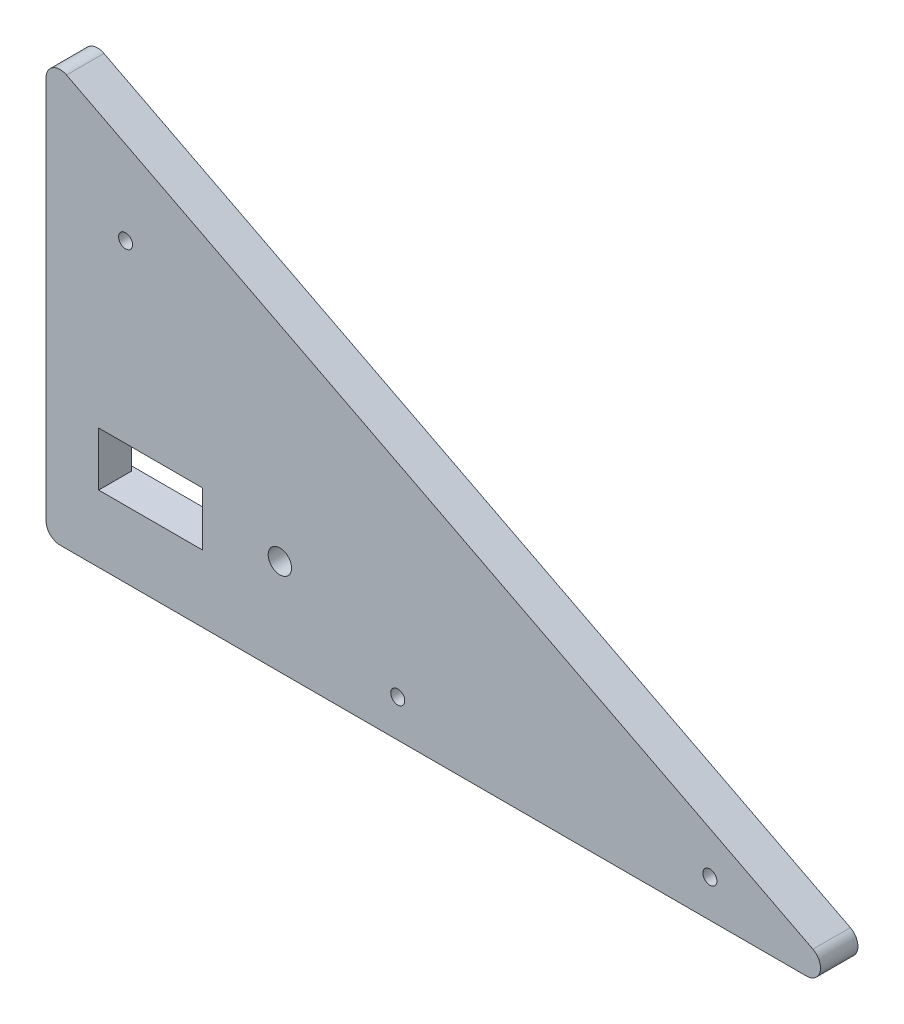
SolidWorks part; units mm, degrees
ref_plane "Front Plane" through (0, 0, 0) normal (0, 0, 1) x (1, 0, 0)
ref_plane "Top Plane" through (0, 0, 0) normal (0, 1, 0) x (1, 0, 0)
ref_plane "Right Plane" through (0, 0, 0) normal (1, 0, 0) x (0, 0, -1)
sketch "Sketch1" plane through (0, 0, 0) normal (0, 0, 1) x (1, 0, 0)
  line L0 (-67.1521, 0) -> (92.455, 0)
  line L1 (93.827, 5.6679) -> (-65.7801, 87.7515)
  line L2 (-70.1521, 85.0837) -> (-70.1521, 3)
  arc A0 (-67.1521, 0) -> (-70.1521, 3) centre (-67.1521, 3) cw
  arc A1 (-65.7801, 87.7515) -> (-70.1521, 85.0837) centre (-67.1521, 85.0837) ccw
  arc A2 (92.455, 0) -> (93.827, 5.6679) centre (92.455, 3) ccw
  point P6 (-70.1521, 0)
  point P9 (-70.1521, 90)
  point P12 (104.8479, 0)
  dimension "D3" = 3
  dimension "D1" = 175
  dimension "D2" = 90
extrude "Boss-Extrude1" add sketch "Sketch1" along normal blind 8
sketch "Sketch3" plane through (0, 0, 0) normal (0, 0, 1) x (1, 0, 0)
  line L0 (-67.1521, 0) -> (92.455, 0) construction
  line L1 (93.827, 5.6679) -> (-65.7801, 87.7515) construction
  circle A0 centre (71.8002, 8) radius 1.5
  circle A1 centre (5.0502, 8) radius 1.5
  dimension "D1" = 3
  dimension "D2" = 3
  dimension "D3" = 66.75
  dimension "D4" = 8
  dimension "D5" = 8
  dimension "D6" = 8
extrude "Cut-Extrude6" cut sketch "Sketch3" against normal blind 30 and the other way blind 30 contours A0 | A1
sketch "Sketch8" plane through (0, 0, 8) normal (0, 0, 1) x (1, 0, 0)
  line L0 (-70.1521, 85.0837) -> (-70.1521, 3) construction
  line L1 (-36.7021, 14.3248) -> (-36.7021, 25.8248)
  line L2 (-58.9021, 14.3248) -> (-58.9021, 25.8248)
  line L3 (-31.7021, 25.8248) -> (-36.7021, 25.8248)
  line L4 (-53.1521, 25.8248) -> (-36.7021, 25.8248)
  line L5 (-58.9021, 25.8248) -> (-53.1521, 25.8248)
  line L6 (-63.9021, 25.8248) -> (-58.9021, 25.8248)
  line L7 (-63.9021, 14.3248) -> (-63.9021, 25.8248)
  line L8 (-63.9021, 14.3248) -> (-58.9021, 14.3248)
  line L9 (-58.9021, 14.3248) -> (-53.1521, 14.3248)
  line L10 (-53.1521, 14.3248) -> (-36.7021, 14.3248)
  line L11 (-31.7021, 14.3248) -> (-36.7021, 14.3248)
  line L12 (-31.7021, 14.3248) -> (-31.7021, 25.8248)
  circle A0 centre (-53.1521, 63.3654) radius 1.5
  circle A1 centre (-53.1521, 20.0748) radius 2.25
  arc A2 (-47.7435, 18.1232) -> (-47.7435, 22.0264) centre (-47.1521, 20.0748) ccw
  arc A3 (-47.7435, 22.0264) -> (-47.7435, 18.1232) centre (-53.1521, 20.0748) ccw
  dimension "D1" = 3
  dimension "D2" = 17
extrude "Cut-Extrude9" cut sketch "Sketch8" against normal blind 20 contours A3 A2 L10 L1 L4 | A3 L5 L2 | A3 L2 L9 | A2 A3 A1 | A1 region at (-42.5058, 20.0748, 8) region at (-57.091, 16.1359, 8) region at (-57.6178, 15.6091, 8) region at (-57.6178, 24.5404, 8) region at (-53.1521, 20.0748, 8)
sketch "Sketch11" plane through (0, 0, 0) normal (0, 0, -1) x (-1, 0, 0)
  line L0 (58.9021, 25.8248) -> (63.9021, 25.8248)
  line L1 (63.9021, 25.8248) -> (63.9021, 14.3248)
  line L2 (63.9021, 14.3248) -> (58.9021, 14.3248)
  line L3 (58.9021, 25.8248) -> (58.9021, 14.3248)
  line L5 (36.7021, 25.8248) -> (31.7021, 25.8248)
  line L6 (31.7021, 25.8248) -> (31.7021, 14.3248)
  line L7 (31.7021, 14.3248) -> (36.7021, 14.3248)
  line L8 (36.7021, 25.8248) -> (36.7021, 14.3248)
  line M14 (36.7021, 14.3248) -> (36.7021, 25.8248)
  line M16 (58.9021, 25.8248) -> (58.9021, 14.3248)
  dimension "D1" = 5
extrude "Cut-Extrude10" cut sketch "Sketch11" against normal blind 1 contours L2 L1 L0 M16 | L6 L7 L5 M14 region at (-61.4021, 20.0748, 0) region at (-34.2021, 20.0748, 0)
extrude "Cut-Extrude11" cut sketch "Sketch8<6>" against normal blind 10 contours A0
sketch "Sketch8<6>" plane through (0, 0, 8) normal (0, 0, 1) x (1, 0, 0) same geometry as "Sketch8"
sketch "Sketch12" plane through (0, 0, 8) normal (0, 0, 1) x (1, 0, 0)
  line L0 (-70.1521, 85.0837) -> (-70.1521, 3) construction
  line L1 (-67.1521, 0) -> (92.455, 0) construction
  circle A0 centre (-20.1521, 20.5) radius 2.5
  dimension "D1" = 5
  dimension "D2" = 50
  dimension "D3" = 20.5
extrude "Cut-Extrude12" cut sketch "Sketch12" against normal blind 20
